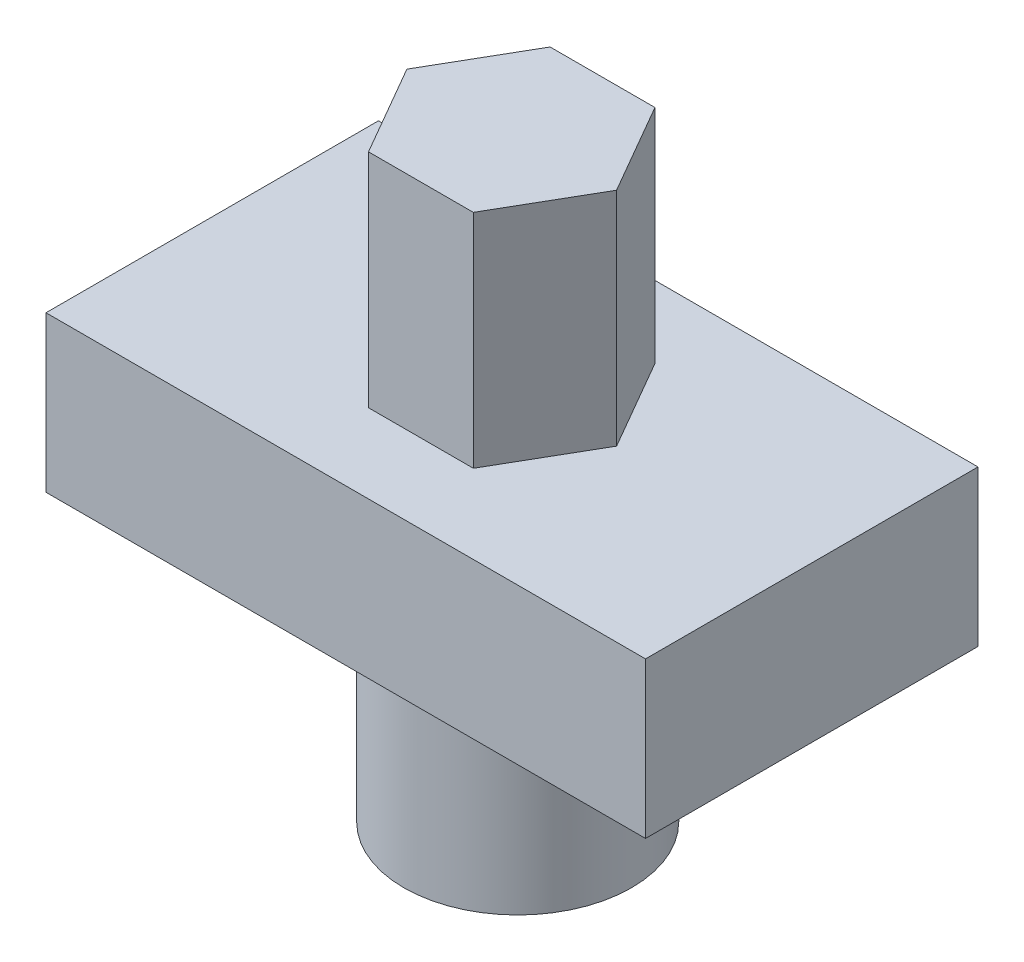
SolidWorks part; units mm, degrees
ref_plane "Front Plane" through (0, 0, 0) normal (0, 0, 1) x (1, 0, 0)
ref_plane "Top Plane" through (0, 0, 0) normal (0, 1, 0) x (1, 0, 0)
ref_plane "Right Plane" through (0, 0, 0) normal (1, 0, 0) x (0, 0, -1)
sketch "Sketch1" plane through (0, 0, 0) normal (0, 0, 1) x (1, 0, 0)
  line L1 (-68.7035, -17.821) -> (68.7035, -17.821)
  line L2 (-68.7035, -17.821) -> (-68.7035, 17.821)
  line L3 (-68.7035, 17.821) -> (68.7035, 17.821)
  line L4 (68.7035, -17.821) -> (68.7035, 17.821)
  line L5 (-68.7035, -17.821) -> (68.7035, 17.821) construction
  line L6 (-68.7035, 17.821) -> (68.7035, -17.821) construction
  point P0 (0, 0)
extrude "Boss-Extrude1" add sketch "Sketch1" along normal blind 76.2 contours L1 L4 L3 L2
sketch "Sketch2" plane through (0, 17.821, 0) normal (0, 1, 0) x (1, 0, 0)
  line L1 (23.159, -37.2907) -> (11.1437, -16.4796)
  line L2 (11.1437, -16.4796) -> (-12.8869, -16.4796)
  line L3 (-12.8869, -16.4796) -> (-24.9022, -37.2907)
  line L4 (-24.9022, -37.2907) -> (-12.8869, -58.1018)
  line L5 (-12.8869, -58.1018) -> (11.1437, -58.1018)
  line L6 (11.1437, -58.1018) -> (23.159, -37.2907)
  circle A0 centre (-0.8716, -37.2907) radius 20.8111 construction
extrude "Boss-Extrude2" add sketch "Sketch2" along normal blind 50.8
sketch "Sketch3" plane through (0, -17.821, 0) normal (0, -1, 0) x (1, 0, 0)
  circle A0 centre (0, 36.7926) radius 26.0998
extrude "Boss-Extrude3" add sketch "Sketch3" along normal blind 50.8
